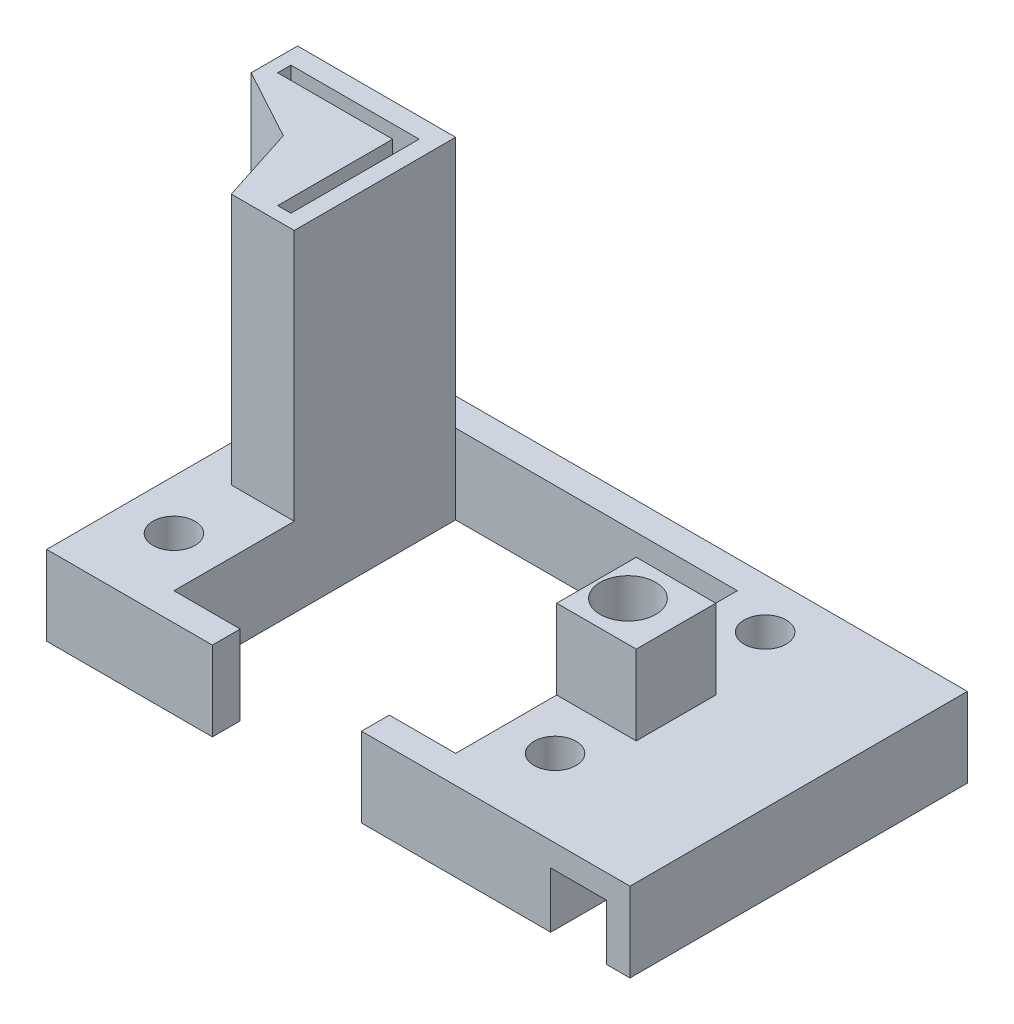
SolidWorks part; units mm, degrees
ref_plane "Front Plane" through (0, 0, 0) normal (0, 0, 1) x (1, 0, 0)
ref_plane "Top Plane" through (0, 0, 0) normal (0, 1, 0) x (1, 0, 0)
ref_plane "Right Plane" through (0, 0, 0) normal (1, 0, 0) x (0, 0, -1)
sketch "Sketch1" plane through (0, 0, 0) normal (0, 1, 0) x (1, 0, 0)
  line L1 (0, 0) -> (42.5, 0)
  line L2 (0, 0) -> (0, 42.5)
  line L3 (0, 42.5) -> (42.5, 42.5)
  line L4 (42.5, 0) -> (42.5, 42.5)
  line L5 (-15, 0) -> (57.5, 0)
  line L6 (-15, 0) -> (-15, 46.7)
  line L7 (-15, 46.7) -> (57.5, 46.7)
  line L8 (57.5, 0) -> (57.5, 46.7)
  line L9 (-15, 0) -> (10, 0)
  line L10 (-15, 0) -> (-15, -4.2)
  line L11 (-15, -4.2) -> (10, -4.2)
  line L12 (10, 0) -> (10, -4.2)
  line L13 (57.5, 0) -> (32.5, 0)
  line L14 (57.5, 0) -> (57.5, -4.2)
  line L15 (57.5, -4.2) -> (32.5, -4.2)
  line L16 (32.5, 0) -> (32.5, -4.2)
  circle A0 centre (-7.5, 7.5) radius 3.175
  circle A2 centre (50, 39.2) radius 3.175
  circle A3 centre (50, 7.5) radius 3.175
  point P11 (-7.5, 7.5)
  point P12 (-7.5, 7.5)
  point P20 (50, 35.5771)
  dimension "D5" = 7.5
  dimension "D7" = 6.35
  dimension "D1" = 42.5
  dimension "D2" = 15
  dimension "D3" = 15
  dimension "D4" = 4.2
  dimension "D6" = 7.5
  dimension "D8" = 7.5
  dimension "D9" = 7.5
  dimension "D10" = 4.2
  dimension "D11" = 10
extrude "Boss-Extrude1" add sketch "Sketch1" along normal blind 12 contours L5 L8 L7 L6 L2 L3 L4 A3 A2 A0 | L12 L1 L5 L10 L11 | L1 L16 L15 L14 L5 region at (-7.5, 0, -0.8624) region at (-2.5, 0, 2.1) region at (45, 0, 2.1)
sketch "Sketch4" plane through (53.3, 0, 4.2) normal (0, 0, -1) x (-1, 0, 0)
  line L0 (-7.75, 8.4) -> (-4.2, 8.4) construction
  line L1 (-19.7, 0) -> (-4.2, 0)
  line L2 (-19.7, 0) -> (-19.7, 12)
  line L3 (-19.7, 12) -> (-4.2, 12)
  line L4 (-4.2, 0) -> (-4.2, 12)
  line L5 (-16.15, 0) -> (-7.75, 0)
  line L6 (-16.15, 0) -> (-16.15, 8.4)
  line L7 (-16.15, 8.4) -> (-7.75, 8.4)
  line L8 (-7.75, 0) -> (-7.75, 8.4)
  line L9 (-16.15, 8.4) -> (-19.7, 8.4) construction
  point P9 (-21.0668, -0.3569)
  point P12 (-4.2, 0)
  line M16 (-4.2, 0) -> (-4.2, 12)
  dimension "D1" = 15.5
  dimension "D2" = 12
  dimension "D3" = 8.4
extrude "Boss-Extrude2" add sketch "Sketch4" along normal up to surface (50.9 mm away) contours L1 L8 L7 L6 L2 L3 L4 M16 region at (72.804, 6, 4.2) up to face at (21.25, 6, -46.7)
sketch "Sketch5" plane through (0, 12, 0) normal (0, 1, 0) x (1, 0, 0)
  line L0 (42.5, 0) -> (42.5, 42.5) construction
  line L1 (42.5, 27.25) -> (54.5, 27.25)
  line L2 (42.5, 27.25) -> (42.5, 15.25)
  line L3 (42.5, 15.25) -> (54.5, 15.25)
  line L4 (54.5, 27.25) -> (54.5, 15.25)
  line L5 (21.25, 42.5) -> (21.25, -4.8094) construction
  line L7 (0, 42.5) -> (42.5, 42.5) construction
  line L8 (54.5, 21.25) -> (42.5, 21.25) construction
  circle A0 centre (47.25, 21.25) radius 4.2
  point P11 (21.25, 42.5)
  point P15 (47.25, 23.778)
  point P16 (42.5, 15.4964)
  point P17 (42.5, 21.25)
  dimension "D2" = 8.4
  dimension "D1" = 26
  dimension "D3" = 12
  dimension "D4" = 12
extrude "Boss-Extrude3" add sketch "Sketch5" along normal blind 12
sketch "Sketch6" plane through (0, 0, 0) normal (0, -1, 0) x (1, 0, 0)
  line L1 (-2.5, -20.15) -> (-4.5, -20.15)
  line L2 (-2.5, -20.15) -> (-2.5, -39.5)
  line L3 (-2.5, -39.5) -> (-21.85, -39.5)
  line L6 (-4.5, -20.15) -> (-4.5, -37.5)
  line L7 (-4.5, -37.5) -> (-21.85, -37.5)
  line L8 (-21.85, -37.5) -> (-21.85, -39.5)
  line L9 (-2.5, -18.15) -> (-9.5, -18.15)
  line L10 (-2.5, -42.5) -> (-23.85, -42.5)
  line L11 (-2.5, -42.5) -> (-2.5, -18.15)
  line L14 (-9.5, -18.15) -> (-13.2006, -29.6987)
  line L15 (-13.2006, -29.6987) -> (-23.85, -35.5)
  line L16 (-23.85, -35.5) -> (-23.85, -42.5)
  line L18 (-2.5, -42.5) -> (0, -42.5)
  line L19 (-2.5, -42.5) -> (-2.5, -18.15)
  line L20 (-2.5, -18.15) -> (0, -18.15)
  line L21 (0, -42.5) -> (0, -18.15)
  point P4 (-2.4481, -39.5856)
  point P5 (0, -42.5)
  point P7 (-17.2129, -47.9873)
  point P10 (-17.4245, -48.769)
  point P16 (-17, -47.3953)
  point P17 (-12.5, -68.3802)
  point P18 (-15, -48.6387)
  line M11 (0, -42.5) -> (0, 0)
  line M15 (-15, 4.2) -> (-15, -46.7)
  dimension "D1" = 19.35
  dimension "D2" = 2
  dimension "D3" = 3
  dimension "D4" = 2
  dimension "D5" = 2
  dimension "D6" = 7
  dimension "D7" = 10.7006
  dimension "D8" = 2.5
  dimension "D9" = 2.5
extrude "Boss-Extrude5" add sketch "Sketch6" against normal blind 50 contours L14 L15 L7 L6 L1 L11 L9 M15 | L15 L16 L10 L3 L8 L7 M15 | L10 L11 L3 M15 | L20 L11 L2 L18 M11 region at (-1.25, 0, -30.325) region at (-8.7333, 0, -28.854) region at (-8.75, 0, -41) region at (-15.1477, 0, -41)
equation "\"8mm hole\" = 8.4mm"
equation "\"22mm hole\"= 23mm"
equation "\"15mm hole\"= 15.8mm"
equation "\"bed height offset\"= 3mm"
equation "\"motor width\"= 42.5mm"
equation "\"D3@Sketch4\"= \"8mm hole\""
equation "\"D2@Sketch5\"= \"8mm hole\""
